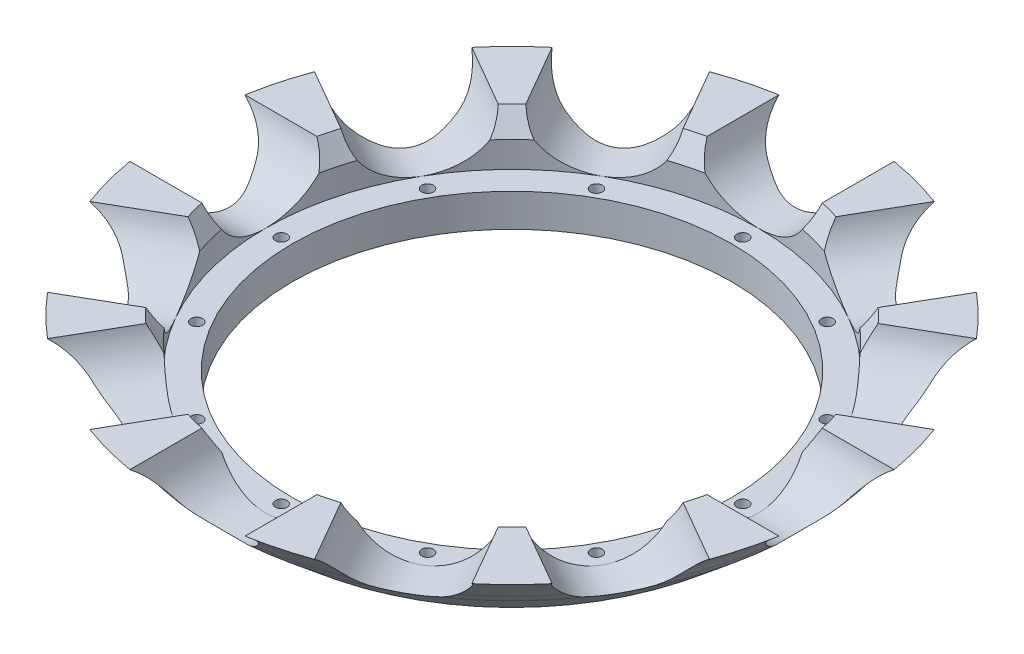
SolidWorks part; units mm, degrees
material "PUR"
ref_plane "Front Plane" through (0, 0, 0) normal (0, 0, 1) x (1, 0, 0)
ref_plane "Top Plane" through (0, 0, 0) normal (0, 1, 0) x (1, 0, 0)
ref_plane "Right Plane" through (0, 0, 0) normal (1, 0, 0) x (0, 0, -1)
sketch "Sketch1" plane through (0, 0, 0) normal (0, 0, 1) x (1, 0, 0)
  line L0 (-60, 9.965) -> (-60, 18.965) construction
  line L1 (-60, 9.965) -> (-60, 18.965)
  line L2 (-66.5, 9.965) -> (-66.5, 18.965) construction
  line L3 (-66.5, 9.965) -> (-66.5, 18.965)
  line L4 (-60, 18.965) -> (-66.5, 18.965)
  line L5 (-60, 9.965) -> (-66.5, 9.965)
  line L6 (0, -200069.0475) -> (0, 200086.9028) construction
  line L7 (0, -200069.0475) -> (0, 200086.9028) construction
revolve "Revolve1" add sketch "Sketch1" angle 360 about L7
sketch "Sketch2" plane through (0, 18.965, 0) normal (0, 1, 0) x (1, 0, 0)
  circle A1 centre (0, 63) radius 1.6
  circle A2 centre (0, 63) radius 1.6
  dimension "D1" = 0
extrude "Cut-Extrude1" cut sketch "Sketch2" against normal through all
pattern_circular "CirPattern1" count 12 over 360 about axis through (0, -200069.0475, 0) along (0, -1, 0) of "Cut-Extrude1"
sketch "Sketch3" plane through (0, 0, 0) normal (0, 0, 1) x (1, 0, 0)
  line L0 (-66.5, 18.965) -> (-66.5, 9.965)
  line L1 (-66.5, 9.965) -> (-78.5, 20.0342)
  line L2 (-66.5, 18.965) -> (-67.3, 18.965)
  line L3 (-67.3, 18.965) -> (-67.3, 20.0342)
  line L4 (-67.3, 20.0342) -> (-78.5, 20.0342) construction
  line L5 (-84.0797, 32) -> (-84.0797, 43.6972) construction
  line L6 (-67.3, 20.0342) -> (-67.3, 26.0342)
  line L7 (-84.0797, 32) -> (-90, 32)
  line L8 (0, 0) -> (0, 39.8275) construction
  line L9 (-84.0797, 32) -> (-70.7444, 32)
  line L10 (-70.7444, 32) -> (-67.3, 26.0342)
  arc A0 (-78.5, 20.0342) -> (-81.2743, 23.0684) centre (-68.4595, 32) cw
  arc A3 (-81.2743, 23.0684) -> (-90, 32) centre (-112.4493, 1.3401) ccw
  arc A4 (-81.2743, 23.0684) -> (-84.0797, 32) centre (-68.4595, 32) cw construction
  point P19 (-84.5368, 28.0828)
  dimension "D8" = 38
  dimension "D1" = 50
  dimension "D2" = 12
  dimension "D3" = 0.8
  dimension "D4" = 32
  dimension "D5" = 6
  dimension "D6" = 150
  dimension "D7" = 90
revolve "Revolve2" add sketch "Sketch3" angle 360 about L8
sketch "Sketch4" plane through (0, 0, 0) normal (0, 0, 1) x (1, 0, 0)
  line L1 (67.3, 18.965) -> (-67.3, 18.965) construction
  line L2 (67.3, 18.965) -> (-67.3, 18.965) construction
  line L4 (0, 0) -> (0, 34.965) construction
  circle A0 centre (0, 34.965) radius 16
  dimension "D1" = 32
extrude "Cut-Extrude2" cut sketch "Sketch4" along normal through all
pattern_circular "CirPattern2" count 12 over 360 about axis through (0, 9.965, 0) along (0, -1, 0) of "Cut-Extrude2"
